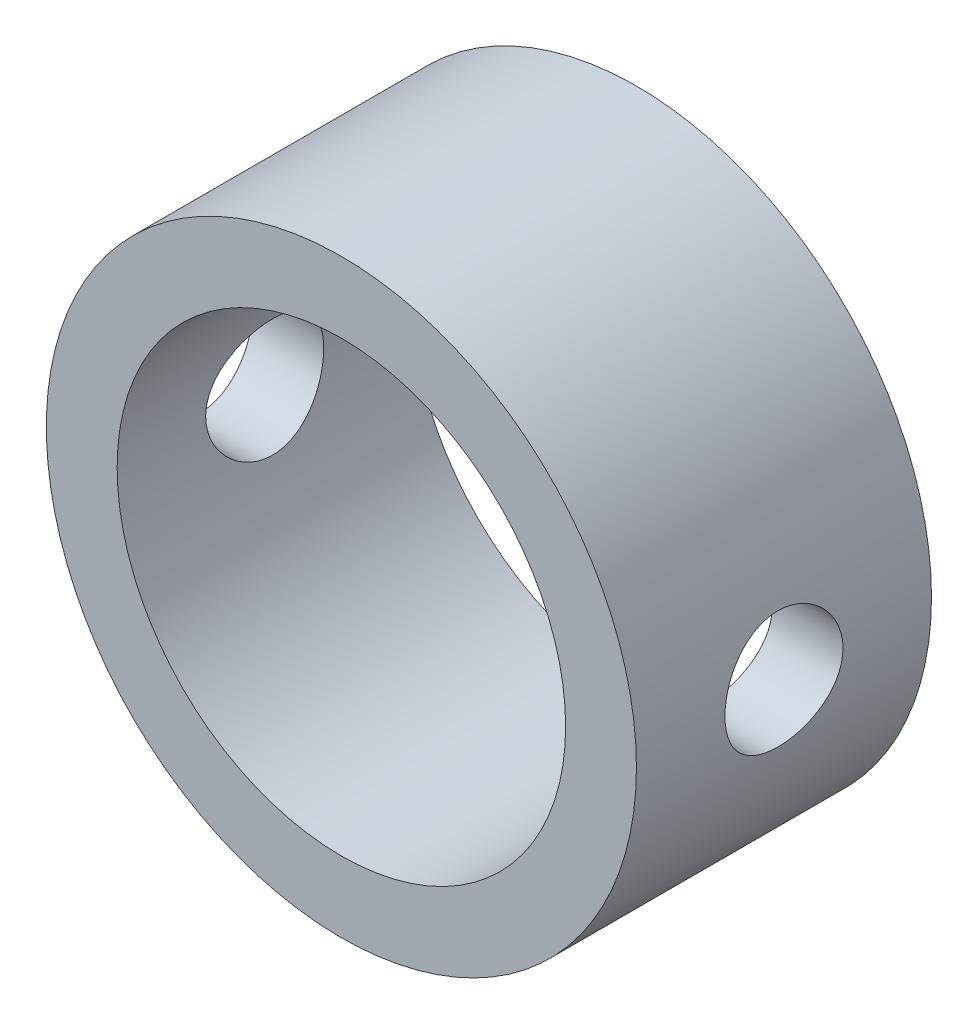
SolidWorks part; units mm, degrees
ref_plane "Plano frontal" through (0, 0, 0) normal (0, 0, 1) x (1, 0, 0)
ref_plane "Plano superior" through (0, 0, 0) normal (0, 1, 0) x (1, 0, 0)
ref_plane "Plano direito" through (0, 0, 0) normal (1, 0, 0) x (0, 0, -1)
sketch "Esboço1" plane through (0, 0, 0) normal (0, 0, 1) x (1, 0, 0)
  circle A0 centre (0, 0) radius 10
  circle A1 centre (0, 0) radius 7.6
  dimension "D1" = 20
  dimension "D2" = 15.2
extrude "Ressalto-extrusão1" add sketch "Esboço1" along normal blind 10
sketch "Esboço2" plane through (0, 0, 0) normal (1, 0, 0) x (0, 0, -1)
  line L0 (0, 10) -> (-10, 10) construction
  circle A0 centre (-5, 0) radius 2
  point P2 (-5, 10)
  point P3 (0, 0)
  point P6 (0, 0)
  dimension "D1" = 4
extrude "Corte-extrusão1" cut sketch "Esboço2" against normal through all both and the other way through all
